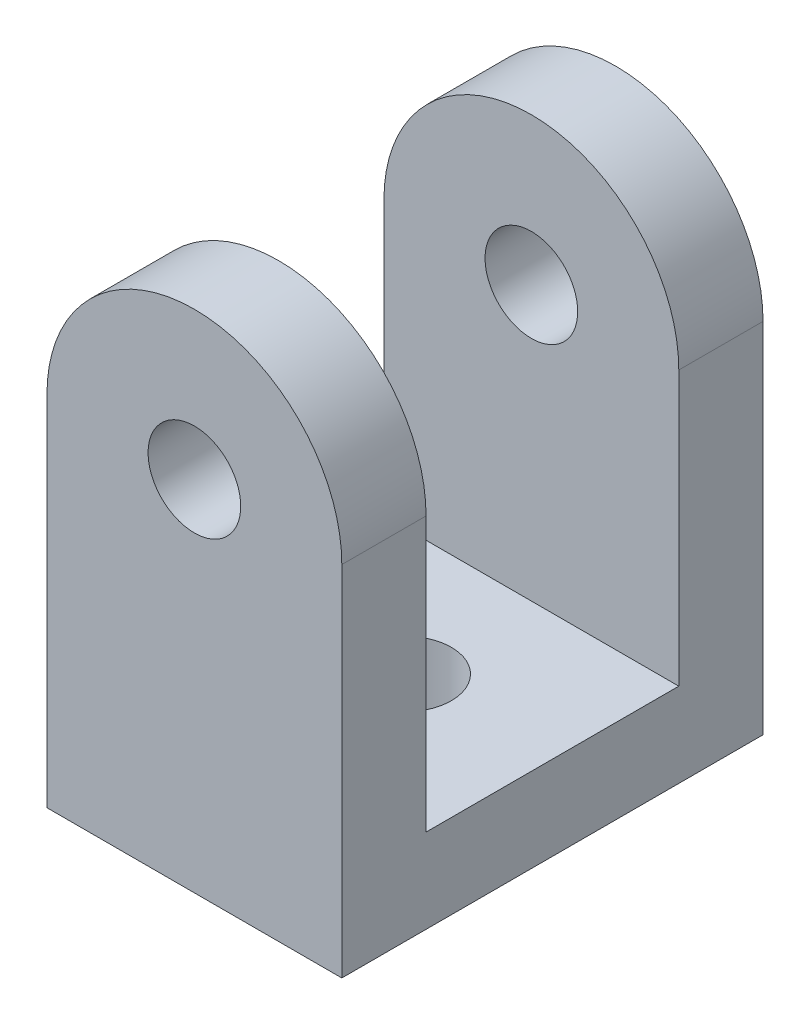
SolidWorks part; units mm, degrees
ref_plane "前视基准面" through (0, 0, 0) normal (0, 0, 1) x (1, 0, 0)
ref_plane "上视基准面" through (0, 0, 0) normal (0, 1, 0) x (1, 0, 0)
ref_plane "右视基准面" through (0, 0, 0) normal (1, 0, 0) x (0, 0, -1)
sketch "草图1" plane through (0, 0, 0) normal (0, 1, 0) x (1, 0, 0)
  line L1 (-3.5, 5) -> (3.5, 5)
  line L2 (-3.5, 5) -> (-3.5, -5)
  line L3 (-3.5, -5) -> (3.5, -5)
  line L4 (3.5, 5) -> (3.5, -5)
  line L5 (-3.5, 5) -> (3.5, -5) construction
  line L6 (-3.5, -5) -> (3.5, 5) construction
  point P0 (0, 0)
  dimension "D1" = 10
  dimension "D2" = 7
extrude "凸台-拉伸1" add sketch "草图1" along normal blind 2
sketch "草图2" plane through (0, 2, 0) normal (0, 1, 0) x (1, 0, 0)
  line L1 (-3.5, -5) -> (3.5, -5)
  line L2 (-3.5, -5) -> (-3.5, -3)
  line L3 (-3.5, -3) -> (3.5, -3)
  line L4 (3.5, -5) -> (3.5, -3)
  line L5 (3.5, -5) -> (3.5, 5) construction
  line L6 (0, 0) -> (2.0362, 0) construction
  line L7 (3.5, 5) -> (3.5, 3)
  line L8 (-3.5, 3) -> (3.5, 3)
  line L9 (-3.5, 5) -> (-3.5, 3)
  line L10 (-3.5, 5) -> (3.5, 5)
  dimension "D1" = 2
  dimension "D2" = 7
extrude "凸台-拉伸2" add sketch "草图2" along normal blind 10
fillet "圆角1" 2 edges at (3.5, 12, 4) (-3.5, 12, 4) type full round first side face at (3.5, 6.5, 0) second side face at (-3.5, 6.5, 0) middle face at (0, 12, 4)
fillet "圆角2" 2 edges at (3.5, 12, -4) (-3.5, 12, -4) type full round first side face at (3.5, 5.625, 0) second side face at (-3.5, 5.625, 0) middle face at (0, 12, -4)
sketch "草图3" plane through (0, 0, -5) normal (0, 0, -1) x (-1, 0, 0)
  circle A0 centre (0, 8.5) radius 1.1
  dimension "D1" = 2.2
extrude "切除-拉伸1" cut sketch "草图3" against normal blind 25
sketch "草图4" plane through (0, 2, 0) normal (0, 1, 0) x (1, 0, 0)
  circle A0 centre (0, 0) radius 1.1
  dimension "D1" = 2.2
extrude "切除-拉伸2" cut sketch "草图4" against normal blind 25
